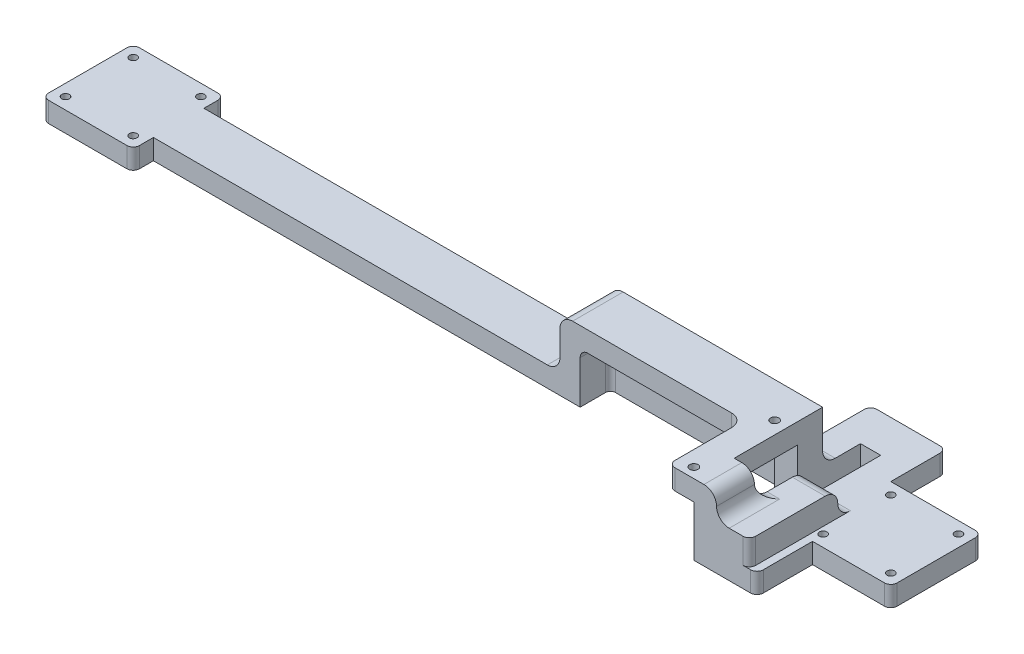
SolidWorks part; units mm, degrees
ref_plane "Front" through (0, 0, 0) normal (0, 0, 1) x (1, 0, 0)
ref_plane "Top" through (0, 0, 0) normal (0, 1, 0) x (1, 0, 0)
ref_plane "Right" through (0, 0, 0) normal (1, 0, 0) x (0, 0, -1)
sketch "Sketch1" plane through (0, 0, 0) normal (0, 1, 0) x (1, 0, 0)
  line L1 (0, 0) -> (264.8, 0) construction
  line L2 (0, 0) -> (0, -156.4) construction
  line L3 (0, -156.4) -> (264.8, -156.4) construction
  line L4 (264.8, 0) -> (264.8, -156.4) construction
  line L5 (0, -68.2) -> (264.8, -68.2)
  line L6 (0, -68.2) -> (0, -88.2)
  line L7 (0, -88.2) -> (264.8, -88.2)
  line L8 (264.8, -68.2) -> (264.8, -88.2)
  line L9 (0, -68.2) -> (-70, -68.2)
  line L10 (0, -68.2) -> (0, -88.2)
  line L11 (0, -88.2) -> (-70, -88.2)
  line L12 (-70, -68.2) -> (-70, -88.2)
  line L13 (264.8, -68.2) -> (334.8, -68.2)
  line L14 (264.8, -68.2) -> (264.8, -88.2)
  line L15 (264.8, -88.2) -> (334.8, -88.2)
  line L16 (334.8, -68.2) -> (334.8, -88.2)
  dimension "D1" = 264.8
  dimension "D2" = 156.4
  dimension "D3" = 20
  dimension "D4" = 68.2
  dimension "D5" = 70
  dimension "D6" = 70
extrude "大梁" add sketch "Sketch1" along normal blind 8 contours L9 L12 L11 L6 | L8 L5 L6 L7 | L16 L13 L8 L15 region at (132.4, 0, 78.2) region at (-35, 0, 78.2) region at (299.8, 0, 78.2)
sketch "Sketch2" plane through (0, 0, 68.2) normal (0, 0, -1) x (-1, 0, 0)
  line L0 (-334.8, 8) -> (70, 8) construction
  line L1 (53.2, 8) -> (17.2, 8)
  line L2 (53.2, 8) -> (53.2, 0)
  line L3 (53.2, 0) -> (17.2, 0)
  line L4 (17.2, 8) -> (17.2, 0)
  line L5 (-334.8, 0) -> (70, 0) construction
  line L6 (70, 8) -> (70, 0) construction
  line L7 (-246.8, 0) -> (-282.8, 0)
  line L8 (-282.8, 8) -> (-282.8, 0)
  line L9 (-246.8, 8) -> (-282.8, 8)
  line L10 (-246.8, 8) -> (-246.8, 0)
  dimension "D1" = 36
  dimension "D2" = 16.8
  dimension "D3" = 2
extrude "Boss-Extrude2" add sketch "Sketch2" along normal blind 8
sketch "Sketch4" plane through (0, 0, 88.2) normal (0, 0, 1) x (1, 0, 0)
  line L0 (334.8, 0) -> (-70, 0) construction
  line L1 (-17.2, 0) -> (-53.2, 0)
  line L2 (-17.2, 0) -> (-17.2, 8)
  line L3 (-17.2, 8) -> (-53.2, 8)
  line L4 (-53.2, 0) -> (-53.2, 8)
  line L5 (334.8, 8) -> (-70, 8) construction
  line L7 (-70, 8) -> (-70, 0) construction
  line L8 (282.8, 0) -> (246.8, 0)
  line L9 (282.8, 8) -> (246.8, 8)
  line L10 (282.8, 0) -> (282.8, 8)
  line L11 (246.8, 0) -> (246.8, 8)
  dimension "D1" = 36
  dimension "D2" = 16.8
  dimension "D3" = 2
extrude "Boss-Extrude3" add sketch "Sketch4" along normal blind 8
sketch "Sketch5" plane through (0, 8, 0) normal (0, 1, 0) x (1, 0, 0)
  line L0 (-53.2, -96.2) -> (-53.2, -88.2) construction
  line L1 (-17.2, -96.2) -> (-53.2, -96.2) construction
  circle A0 centre (-48.6, -91.6) radius 1.5
  circle A1 centre (-21.8, -91.6) radius 1.5
  circle A2 centre (-21.8, -64.8) radius 1.5
  circle A3 centre (-48.6, -64.8) radius 1.5
  circle A4 centre (278.2, -91.6) radius 1.5
  circle A5 centre (251.4, -64.8) radius 1.5
  circle A6 centre (278.2, -64.8) radius 1.5
  circle A7 centre (251.4, -91.6) radius 1.5
  dimension "D1" = 3
  dimension "D2" = 4.6
  dimension "D3" = 4.6
  dimension "D4" = 2
  dimension "D5" = 2
  dimension "D6" = 2
extrude "Cut-Extrude1" cut sketch "Sketch5" against normal through all
fillet "Fillet1" radius 2.5 6 edges at (282.8, 4, 60.2) (282.8, 4, 96.2) (-53.2, 4, 96.2) (-17.2, 4, 96.2) (-53.2, 4, 60.2) (-17.2, 4, 60.2)
sketch "Sketch6" plane through (0, 8, 0) normal (0, 1, 0) x (1, 0, 0)
  line L1 (334.8, -68.2) -> (282.8, -68.2)
  line L2 (334.8, -68.2) -> (334.8, -88.2)
  line L3 (334.8, -88.2) -> (282.8, -88.2)
  line L4 (282.8, -68.2) -> (282.8, -88.2)
extrude "Cut-Extrude2" cut sketch "Sketch6" against normal through all
sketch "Sketch7" plane through (0, 0, 0) normal (0, -1, 0) x (-1, 0, 0)
  line L1 (70, -88.2) -> (53.2, -88.2)
  line L2 (70, -88.2) -> (70, -68.2)
  line L3 (70, -68.2) -> (53.2, -68.2)
  line L4 (53.2, -88.2) -> (53.2, -68.2)
extrude "Cut-Extrude3" cut sketch "Sketch7" against normal through all
sketch "Sketch8" plane through (0, 0, 88.2) normal (0, 0, 1) x (1, 0, 0)
  line L0 (246.8, 8) -> (-17.2, 8) construction
  line L1 (246.8, 0) -> (216.8, 0)
  line L2 (246.8, 0) -> (246.8, 8)
  line L3 (246.8, 8) -> (216.8, 8)
  line L4 (216.8, 0) -> (216.8, 8)
  dimension "D1" = 30
extrude "Boss-Extrude4" add sketch "Sketch8" along normal blind 30
sketch "Sketch9" plane through (0, 0, 68.2) normal (0, 0, -1) x (-1, 0, 0)
  line L1 (-246.8, 8) -> (-216.8, 8)
  line L2 (-246.8, 8) -> (-246.8, 0)
  line L3 (-246.8, 0) -> (-216.8, 0)
  line L4 (-216.8, 8) -> (-216.8, 0)
  dimension "D1" = 30
extrude "Boss-Extrude5" add sketch "Sketch9" along normal blind 30
sketch "Sketch10" plane through (0, 0, 0) normal (0, -1, 0) x (-1, 0, 0)
  line L0 (-216.8, -118.2) -> (-246.8, -118.2) construction
  line L1 (-235.8, -103.2) -> (-227.8, -103.2)
  line L2 (-235.8, -103.2) -> (-235.8, -53.2)
  line L3 (-235.8, -53.2) -> (-227.8, -53.2)
  line L4 (-227.8, -103.2) -> (-227.8, -53.2)
  line L5 (-216.8, -38.2) -> (-216.8, -68.2) construction
  dimension "D1" = 8
  dimension "D2" = 50
  dimension "D3" = 15
  dimension "D4" = 11
extrude "Cut-Extrude4" cut sketch "Sketch10" against normal through all
sketch "Sketch12" plane through (0, 8, 0) normal (0, 1, 0) x (1, 0, 0)
  line L0 (227.8, -103.2) -> (227.8, -53.2) construction
  line L1 (216.8, -118.2) -> (227.8, -118.2)
  line L2 (216.8, -118.2) -> (216.8, -68.2)
  line L3 (216.8, -68.2) -> (227.8, -68.2)
  line L4 (227.8, -118.2) -> (227.8, -68.2)
  point P9 (0, 0)
  point P10 (0, 0)
  dimension "D1" = 50
extrude "Boss-Extrude6" add sketch "Sketch12" along normal blind 17
sketch "Sketch13" plane through (0, 8, 0) normal (0, 1, 0) x (1, 0, 0)
  line L1 (227.8, -118.2) -> (235.8, -118.2)
  line L2 (227.8, -118.2) -> (227.8, -103.2)
  line L3 (227.8, -103.2) -> (235.8, -103.2)
  line L4 (235.8, -118.2) -> (235.8, -103.2)
extrude "Boss-Extrude7" add sketch "Sketch13" along normal blind 17
sketch "Sketch15" plane through (0, 0, 0) normal (0, -1, 0) x (-1, 0, 0)
  line L0 (-227.8, -103.2) -> (-227.8, -53.2) construction
  line L1 (-216.8, -118.2) -> (-227.8, -118.2)
  line L2 (-216.8, -118.2) -> (-216.8, -73.2)
  line L3 (-216.8, -73.2) -> (-227.8, -73.2)
  line L4 (-227.8, -118.2) -> (-227.8, -73.2)
  dimension "D1" = 45
extrude "Cut-Extrude6" cut sketch "Sketch15" against normal blind 20
sketch "Sketch16" plane through (246.8, 0, 0) normal (1, 0, 0) x (0, 0, -1)
  line L0 (-96.2, 8) -> (-96.2, 0) construction
  line L1 (-118.2, 0) -> (-96.2, 0)
  line L2 (-118.2, 0) -> (-118.2, 8)
  line L3 (-118.2, 8) -> (-96.2, 8)
  line L4 (-96.2, 0) -> (-96.2, 8)
extrude "Boss-Extrude9" add sketch "Sketch16" along normal blind 5
sketch "Sketch18" plane through (0, 8, 0) normal (0, 1, 0) x (1, 0, 0)
  line L1 (235.8, -118.2) -> (248.8, -118.2)
  line L2 (235.8, -118.2) -> (235.8, -78.2)
  line L3 (235.8, -78.2) -> (248.8, -78.2)
  line L4 (248.8, -118.2) -> (248.8, -78.2)
  dimension "D1" = 3
  dimension "D2" = 40
extrude "Boss-Extrude10" add sketch "Sketch18" along normal blind 10
sketch "Sketch17" plane through (0, 0, 0) normal (0, -1, 0) x (-1, 0, 0)
  line L0 (-227.8, -103.2) -> (-227.8, -118.2) construction
  line L1 (-227.8, -110.2) -> (-243.8, -110.2)
  line L2 (-227.8, -110.2) -> (-227.8, -88.2)
  line L3 (-227.8, -88.2) -> (-243.8, -88.2)
  line L4 (-243.8, -110.2) -> (-243.8, -88.2)
  line L5 (-227.8, -118.2) -> (-251.8, -118.2) construction
  line L6 (-251.8, -118.2) -> (-251.8, -96.2) construction
  dimension "D1" = 22
  dimension "D2" = 8
  dimension "D3" = 8
sketch "Sketch21" plane through (0, 18, 0) normal (0, 1, 0) x (1, 0, 0)
  line L0 (235.8, -78.2) -> (235.8, -103.2) construction
  line L1 (248.8, -78.2) -> (235.8, -78.2)
  line L2 (248.8, -78.2) -> (248.8, -83.2)
  line L3 (248.8, -83.2) -> (235.8, -83.2)
  line L4 (235.8, -78.2) -> (235.8, -83.2)
  dimension "D1" = 5
extrude "Cut-Extrude9" cut sketch "Sketch21" against normal blind 10
extrude "Cut-Extrude7" cut sketch "Sketch17" against normal blind 12
sketch "Sketch19" plane through (0, 8, 0) normal (0, 1, 0) x (1, 0, 0)
  line L0 (216.8, -88.2) -> (-17.2, -88.2) construction
  line L1 (216.8, -68.2) -> (146.8, -68.2)
  line L2 (216.8, -68.2) -> (216.8, -88.2)
  line L3 (216.8, -88.2) -> (146.8, -88.2)
  line L4 (146.8, -68.2) -> (146.8, -88.2)
  dimension "D1" = 70
extrude "Boss-Extrude11" add sketch "Sketch19" along normal blind 17
sketch "Sketch20" plane through (0, 0, 0) normal (0, -1, 0) x (-1, 0, 0)
  line L0 (-216.8, -88.2) -> (17.2, -88.2) construction
  line L1 (-216.8, -73.2) -> (-151.8, -73.2)
  line L2 (-216.8, -73.2) -> (-216.8, -88.2)
  line L3 (-216.8, -88.2) -> (-151.8, -88.2)
  line L4 (-151.8, -73.2) -> (-151.8, -88.2)
  dimension "D1" = 65
extrude "Cut-Extrude8" cut sketch "Sketch20" against normal blind 20
sketch "Sketch22" plane through (146.8, 0, 0) normal (-1, 0, 0) x (0, 0, 1)
  line L1 (68.2, 8) -> (88.2, 8)
  line L2 (68.2, 8) -> (68.2, 25)
  line L3 (68.2, 25) -> (88.2, 25)
  line L4 (88.2, 8) -> (88.2, 25)
extrude "Boss-Extrude12" add sketch "Sketch22" along normal blind 3
sketch "Sketch23" plane through (0, 25, 0) normal (0, 1, 0) x (1, 0, 0)
  line L0 (143.8, -68.2) -> (143.8, -88.2)
  line L1 (143.8, -88.2) -> (216.8, -88.2)
  line L2 (216.8, -88.2) -> (216.8, -118.2)
  line L3 (216.8, -118.2) -> (235.8, -118.2)
  line L4 (235.8, -118.2) -> (235.8, -103.2)
  line L5 (235.8, -103.2) -> (227.8, -103.2)
  line L6 (227.8, -103.2) -> (227.8, -68.2)
  line L7 (227.8, -68.2) -> (143.8, -68.2)
extrude "Boss-Extrude13" add sketch "Sketch23" along normal blind 3
sketch "Sketch24" plane through (0, 20, 0) normal (0, -1, 0) x (-1, 0, 0)
  line L0 (-227.8, -118.2) -> (-216.8, -118.2) construction
  line L1 (-227.8, -103.2) -> (-227.8, -118.2) construction
  circle A0 centre (-222.8, -114.2) radius 1.65
  circle A1 centre (-222.8, -82.2) radius 1.65
  dimension "D1" = 3.3
  dimension "D2" = 4
  dimension "D3" = 5
  dimension "D4" = 2
extrude "Cut-Extrude10" cut sketch "Sketch24" against normal through all
sketch "Sketch25" plane through (227.8, 0, 0) normal (-1, 0, 0) x (0, 0, 1)
  line L0 (103.2, 20) -> (103.2, 12)
  line L1 (103.2, 12) -> (110.2, 12)
  line L2 (110.2, 12) -> (110.2, 0)
  line L3 (110.2, 0) -> (118.2, 0)
  line L4 (118.2, 0) -> (118.2, 20)
  line L5 (118.2, 20) -> (103.2, 20)
extrude "Boss-Extrude14" add sketch "Sketch25" along normal blind 1
fillet "Fillet4" radius 5 1 edges at (143.8, 8, 78.2)
fillet "Fillet5" radius 5 1 edges at (143.8, 28, 78.2)
fillet "Fillet7" radius 5 1 edges at (222.3, 8, 68.2)
fillet "Fillet8" radius 5 1 edges at (235.8, 18, 110.7)
fillet "Fillet9" radius 5 1 edges at (235.8, 28, 110.7)
fillet "Fillet10" radius 5 1 edges at (216.8, 6.5, 68.2)
fillet "Fillet11" radius 5 1 edges at (242.3, 8, 83.2)
fillet "Fillet12" radius 5 1 edges at (242.3, 18, 83.2)
fillet "Fillet13" radius 5 1 edges at (216.8, 24, 88.2)
fillet "Fillet14" radius 2.5 2 edges at (246.8, 4, 38.2) (216.8, 4, 38.2)
fillet "Fillet15" radius 2.5 2 edges at (216.8, 24, 118.2) (251.8, 4, 118.2)
fillet "Fillet16" radius 2.5 1 edges at (248.8, 13, 118.2)
fillet "Fillet17" radius 5 1 edges at (238.3, 18, 103.2)
sketch "Sketch26" plane through (0, 0, 73.2) normal (0, 0, 1) x (1, 0, 0)
  line L1 (151.8, 0) -> (227.8, 0)
  line L2 (151.8, 0) -> (151.8, 20)
  line L3 (151.8, 20) -> (227.8, 20)
  line L4 (227.8, 0) -> (227.8, 20)
extrude "Boss-Extrude15" add sketch "Sketch26" along normal blind 3
fillet "Fillet18" radius 3 1 edges at (151.8, 20, 82.2)
sketch "Sketch27" plane through (0, 0, 76.2) normal (0, 0, 1) x (1, 0, 0)
  line L0 (227.8, 20) -> (154.8, 20) construction
  line L1 (227.8, 0) -> (218.8, 0)
  line L2 (227.8, 0) -> (227.8, 20)
  line L3 (227.8, 20) -> (218.8, 20)
  line L4 (218.8, 0) -> (218.8, 20)
  dimension "D1" = 9
extrude "Boss-Extrude16" add sketch "Sketch27" along normal blind 2
fillet "Fillet20" radius 2 3 edges at (151.8, 8.5, 76.2) (152.6787, 19.1213, 76.2) (186.8, 20, 76.2)
equation "\"offset\"= 0.3"
equation "\"v\"= 0.1"
equation "\"D1@Cut-Extrude6\"=20"
equation "\"D1@Sketch24\"=\"offset\"+3"
